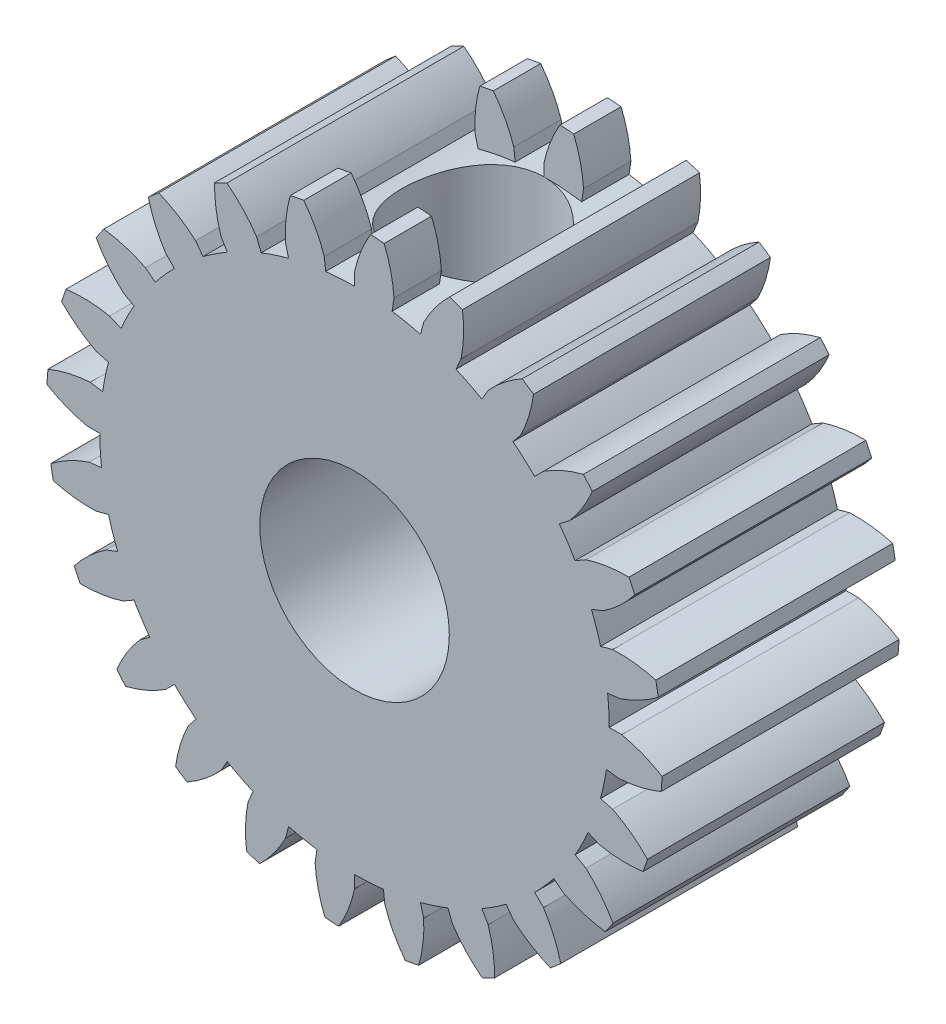
SolidWorks part; units mm, degrees
ref_plane "Front Plane" through (0, 0, 0) normal (0, 0, 1) x (1, 0, 0)
ref_plane "Top Plane" through (0, 0, 0) normal (0, 1, 0) x (1, 0, 0)
ref_plane "Right Plane" through (0, 0, 0) normal (1, 0, 0) x (0, 0, -1)
sketch "Gear" plane through (0, 0, 0) normal (0, 0, 1) x (1, 0, 0)
  circle A0 centre (0, 0) radius 6
  circle A1 centre (0, 0) radius 6.5
  circle A2 centre (0, 0) radius 5.375
  circle A3 centre (0, 0) radius 5.5
  circle A4 centre (0, 0) radius 5.6382
  dimension "Pitch" = 12
  dimension "Addendum" = 13
  dimension "Root" = 10.75
  dimension "Clearance" = 11
  dimension "Base" = 11.2763
sketch "Involute" plane through (0, 0, 0) normal (0, 0, 1) x (1, 0, 0)
  line L0 (0, 0) -> (0, 5.6382)
  line L1 (0, 0) -> (2.8191, 4.8828) construction
  line L2 (0, 0) -> (4.8828, 2.8191) construction
  line L3 (0, 0) -> (5.6382, 0) construction
  line L4 (5.6382, 0) -> (5.6382, 8.8564) construction
  line L5 (4.8828, 2.8191) -> (1.9307, 7.9323) construction
  line L6 (2.8191, 4.8828) -> (0.2625, 6.3589) construction
  line L7 (0, 0) -> (0.7832, 5.9487) construction
  line L8 (0, 0) -> (1.5529, 5.7956)
  line L9 (0.444, 5.9836) -> (0, 0) construction
  circle A0 centre (0, 0) radius 5.6382 construction
  circle A1 centre (0, 0) radius 6 construction
  arc A3 (0.7832, 5.9487) -> (0.1034, 5.9991) centre (0, 0) ccw
  spline S0 degree 3 poles (0, 5.6382) (0.496, 7.9471) (3.7355, 8.8594) (5.6382, 8.8564) knots 0 0 0 0 1 1 1 1
  spline S1 degree 3 poles (0.8321, 5.5764) (0.6823, 7.9332) (-2.3871, 9.3137) (-4.2693, 9.5915) knots 0 0 0 0 1 1 1 1
  point P10 (0, 0)
  dimension "Involute Control" = 90
  dimension "Base Circle Quarter Circumference" = 8.8564
  dimension "D1" = 5.9043
  dimension "D2" = 2.9521
  dimension "Circular Pitch" = 15
  dimension "Involute Array" = 4
sketch "Sketch3" plane through (0, 0, 0) normal (0, 0, 1) x (1, 0, 0)
  line L0 (0.8321, 5.5764) -> (0.7933, 5.3161)
  line L2 (0, 5.6382) -> (0, 5.375)
  arc A2 (0.3368, 6.4913) -> (0, 5.6382) centre (2.7472, 5.0468) ccw
  circle A10 centre (0, 0) radius 5.375 construction
  circle A11 centre (0, 0) radius 5.6382 construction
  arc A17 (0.8321, 5.5764) -> (0.625, 6.4699) centre (-1.9723, 5.3969) ccw
  arc A18 (0.7933, 5.3161) -> (0, 5.375) centre (0, 0) ccw
  arc A19 (0.625, 6.4699) -> (0.3368, 6.4913) centre (0, 0) ccw
  circle A20 centre (0, 0) radius 6.5 construction
  spline S1 degree 3 poles (0.8321, 5.5764) (0.6823, 7.9332) (-2.3871, 9.3137) (-4.2693, 9.5915) knots 0 0 0 0 1 1 1 1 construction
  spline S2 degree 3 poles (0, 5.6382) (0.496, 7.9471) (3.7355, 8.8594) (5.6382, 8.8564) knots 0 0 0 0 1 1 1 1 construction
extrude "Boss-Extrude1" add sketch "Sketch3" along normal blind 5
ref_axis "Axis1" through (0, 0, 0) along (0, 0, 1)
pattern_circular "CirPattern1" count 24 over 360 about axis through (0, 0, 0) along (0, 0, 1) of bodies 101
sketch "Sketch6" plane through (0, 0, 0) normal (0, 0, 1) x (1, 0, 0)
  circle A0 centre (0, 0) radius 5.375 construction
  circle A1 centre (0, 0) radius 5.375
  circle A2 centre (0, 0) radius 2
  dimension "D1" = 4
extrude "Boss-Extrude3" add sketch "Sketch6" along normal up to surface (5 mm away) up to face at (-1.0887, 5.7311, 5)
sketch "Sketch7" plane through (0, 0, 0) normal (0, 1, 0) x (1, 0, 0)
  line L0 (0, -5) -> (0, 0) construction
  circle A0 centre (0, -2.5) radius 1.5
  dimension "D1" = 3
extrude "Cut-Extrude1" cut sketch "Sketch7" along normal up to surface (6.5 mm away) up to face at (0.4809, 6.4814, 2.5)
sketch "Sketch8" plane through (0, 0, 0) normal (0, 1, 0) x (1, 0, 0)
  line L1 (-1.5, -4) -> (1.5, -4)
  line L2 (-1.5, -4) -> (-1.5, -1)
  line L3 (-1.5, -1) -> (1.5, -1)
  line L4 (1.5, -4) -> (1.5, -1)
  line L5 (-1.5, -4) -> (1.5, -1) construction
  line L6 (-1.5, -1) -> (1.5, -4) construction
  line L7 (-6.4699, -5) -> (-6.4699, 0) construction
  point P0 (0, -2.5)
  point P5 (0, 0)
  point P6 (0, 0)
  point P10 (-6.4699, -2.5)
  dimension "D1" = 3
extrude "Cut-Extrude2" cut sketch "Sketch8" along direction (0, 1, 0) on the side against the normal up to surface (4.8385 mm away) from offset 10 up to face at (1.101, 5.2566, 0.7728)
equation "\"Module\"= .5"
equation "\"Teeth\"= 24"
equation "\"Pressure Angle\"= 20deg"
equation "\"Pitch@Gear\"= \"Module\" * \"Teeth\""
equation "\"Addendum@Gear\" = \"Pitch@Gear\" +  ( \"Module\" * 2 ) "
equation "\"Clearance@Gear\" = \"Pitch@Gear\" - ( \"Module\" * 2 )"
equation "\"Root@Gear\"= \"Pitch@Gear\" - ( ( \"Module\" * 1.25 ) * 2 )"
equation "\"Base@Gear\"= \"Pitch@Gear\" * cos ( \"Pressure Angle\" )"
equation "\"Circular Pitch@Involute\"=360/\"Teeth\""
equation "\"Base Circle Quarter Circumference@Involute\"= \"Base@Gear\" * pi / 4"
equation "\"D1@Involute\"= \"Base Circle Quarter Circumference@Involute\" / 3 * 2"
equation "\"D2@Involute\"= \"Base Circle Quarter Circumference@Involute\" / 3"
equation "\"D1@CirPattern1\"= \"Teeth\""
